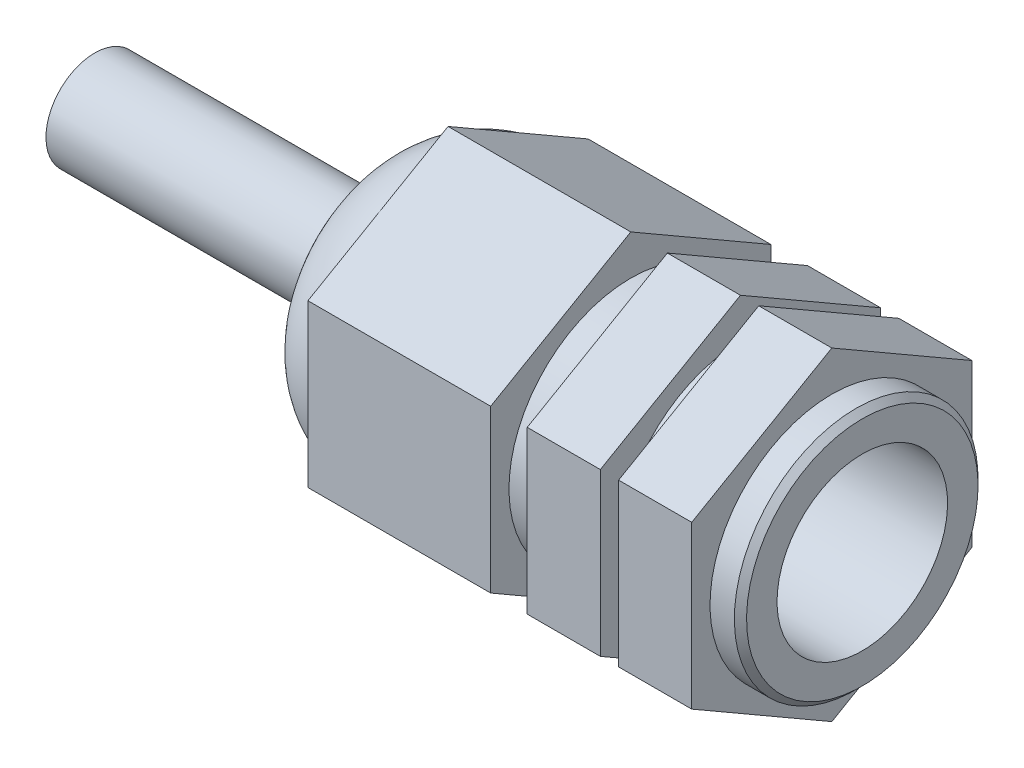
SolidWorks part; units mm, degrees
material "Black Derlin"
ref_plane "Front Plane" through (0, 0, 0) normal (0, 0, 1) x (1, 0, 0)
ref_plane "Top Plane" through (0, 0, 0) normal (0, 1, 0) x (1, 0, 0)
ref_plane "Right Plane" through (0, 0, 0) normal (1, 0, 0) x (0, 0, -1)
sketch "Sketch1" plane through (0, 0, 0) normal (0, 0, 1) x (1, 0, 0)
  line L0 (72.2873, 0) -> (0, 0) construction
  line L1 (5, 7) -> (40, 7)
  line L2 (40, 7) -> (40, 10)
  line L3 (40, 10) -> (30, 10)
  line L4 (30, 10) -> (30, 11.5)
  line L5 (30, 11.5) -> (24, 11.5)
  line L6 (24, 11.5) -> (24, 10)
  line L7 (24, 10) -> (21, 10)
  line L8 (21, 10) -> (21, 11.5)
  line L9 (21, 11.5) -> (7, 11.5)
  line L10 (0, 4.5) -> (0, 3.5)
  line L11 (0, 3.5) -> (5, 3.5)
  line L12 (5, 3.5) -> (5, 7)
  arc A0 (7, 11.5) -> (0, 4.5) centre (7, 4.5) ccw
  dimension "D10" = 7
  dimension "D1" = 14
  dimension "D2" = 20
  dimension "D3" = 23
  dimension "D4" = 23
  dimension "D5" = 10
  dimension "D6" = 6
  dimension "D7" = 40
  dimension "D8" = 20
  dimension "D9" = 3
  dimension "D11" = 5
  dimension "D12" = 7
revolve "Revolve1" add sketch "Sketch1" angle 360 about L0
chamfer "Chamfer1" distance 0.5 angle 45 1 edges at (40, 10, 0)
sketch "Sketch2" plane through (30, 0, 0) normal (1, 0, 0) x (0, 0, -1)
  line L1 (0, 13.2791) -> (-11.5, 6.6395)
  line L2 (-11.5, 6.6395) -> (-11.5, -6.6395)
  line L3 (-11.5, -6.6395) -> (0, -13.2791)
  line L4 (0, -13.2791) -> (11.5, -6.6395)
  line L5 (11.5, -6.6395) -> (11.5, 6.6395)
  line L6 (11.5, 6.6395) -> (0, 13.2791)
  circle A0 centre (0, 0) radius 10 construction
  circle A1 centre (0, 0) radius 10
  circle A2 centre (0, 0) radius 11.5 construction
  circle A3 centre (0, 0) radius 11.5 construction
extrude "Boss-Extrude1" add sketch "Sketch2" against normal blind 6
sketch "Sketch3" plane through (21, 0, 0) normal (1, 0, 0) x (0, 0, -1)
  line L6 (0, 13.2791) -> (-11.5, 6.6395)
  line L7 (-11.5, 6.6395) -> (-11.5, -6.6395)
  line L8 (-11.5, -6.6395) -> (0, -13.2791)
  line L9 (0, -13.2791) -> (11.5, -6.6395)
  line L10 (11.5, -6.6395) -> (11.5, 6.6395)
  line L11 (11.5, 6.6395) -> (0, 13.2791)
  line L12 (0, 13.2791) -> (-11.5, 6.6395)
  line L13 (-11.5, 6.6395) -> (-11.5, -6.6395)
  line L14 (-11.5, -6.6395) -> (0, -13.2791)
  line L15 (0, -13.2791) -> (11.5, -6.6395)
  line L16 (11.5, -6.6395) -> (11.5, 6.6395)
  line L17 (11.5, 6.6395) -> (0, 13.2791)
  circle A1 centre (0, 0) radius 10
  circle A2 centre (0, 0) radius 10
  dimension "D1" = 0
  dimension "D2" = 0
extrude "Boss-Extrude2" add sketch "Sketch3" against normal blind 15
extrude "Boss-Extrude3" add sketch "Sketch2<2>" along normal blind 6 from offset 1.5 separate body
sketch "Sketch2<2>" plane through (30, 0, 0) normal (1, 0, 0) x (0, 0, -1) same geometry as "Sketch2"
sketch "Sketch4" plane through (5, 0, 0) normal (1, 0, 0) x (0, 0, -1)
  circle A0 centre (0, 0) radius 4
  dimension "D1" = 8
extrude "Boss-Extrude4" add sketch "Sketch4" against normal blind 28 separate body
